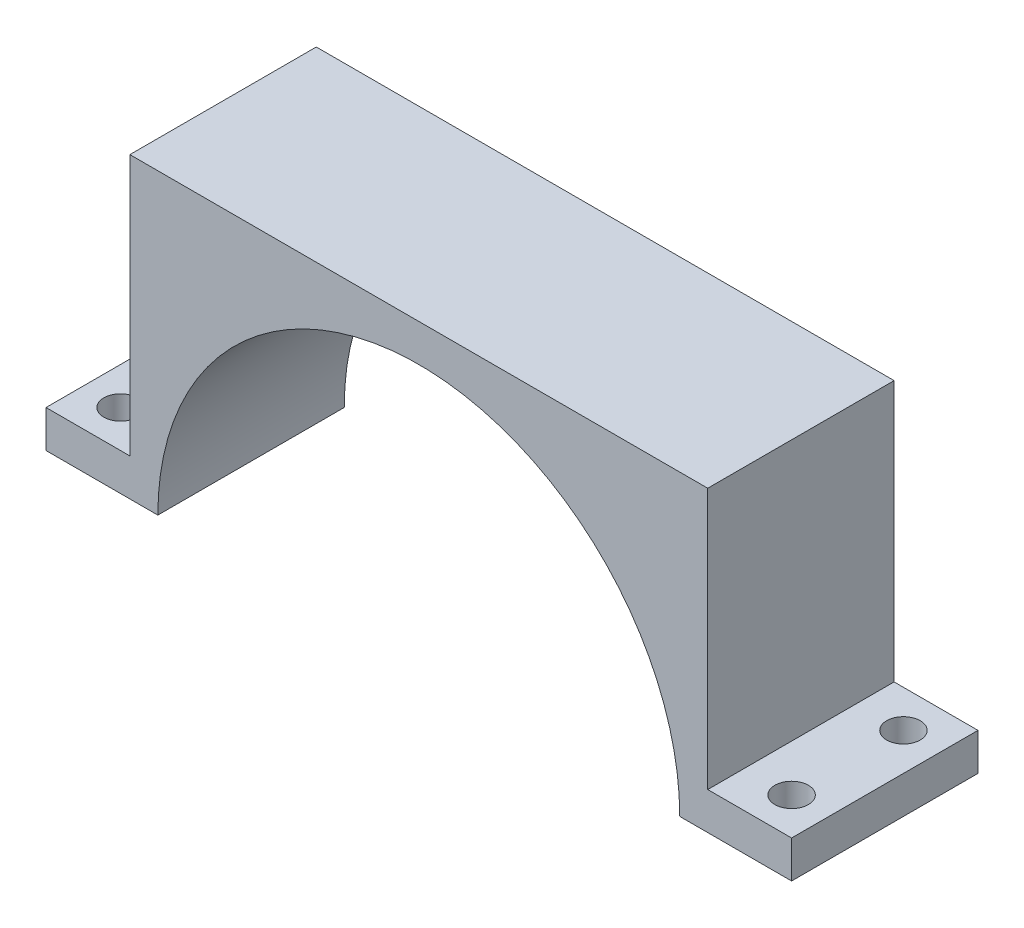
SolidWorks part; units mm, degrees
ref_plane "Płaszczyzna przednia" through (0, 0, 0) normal (0, 0, 1) x (1, 0, 0)
ref_plane "Płaszczyzna górna" through (0, 0, 0) normal (0, 1, 0) x (1, 0, 0)
ref_plane "Płaszczyzna prawa" through (0, 0, 0) normal (1, 0, 0) x (0, 0, -1)
sketch "Szkic1" plane through (0, 0, 0) normal (0, 0, 1) x (1, 0, 0)
  line L0 (70, 0) -> (100, 0)
  line L1 (100, 0) -> (100, 10)
  line L2 (100, 10) -> (77.5, 10)
  line L3 (77.5, 10) -> (77.5, 80)
  line L4 (77.5, 80) -> (-77.5, 80)
  line L5 (-77.5, 80) -> (-77.5, 10)
  line L6 (-77.5, 10) -> (-100, 10)
  line L7 (-100, 10) -> (-100, 0)
  line L8 (-100, 0) -> (-70, 0)
  line L9 (0, -15.2195) -> (0, 87.4692) construction
  arc A0 (-70, 0) -> (70, 0) centre (0, 0) cw
  point P16 (0, 80)
  dimension "D1" = 70
  dimension "D2" = 10
  dimension "D3" = 80
  dimension "D4" = 155
  dimension "D5" = 90
  dimension "D6" = 10
  dimension "D7" = 30
  dimension "D8" = 30
extrude "Dodanie-wyciągnięcie1" add sketch "Szkic1" along normal blind 50
ref_plane "Płaszczyzna1" through (0, 10, 0) normal (0, 1, 0) x (1, 0, 0)
sketch "Szkic2" plane through (0, 10, 0) normal (0, 1, 0) x (1, 0, 0)
  line L0 (-77.5, 0) -> (-100, 0) construction
  line L1 (-100, -50) -> (-100, 0) construction
  line L2 (-77.5, -50) -> (-100, -50) construction
  circle A0 centre (-90, -10) radius 4.5
  circle A1 centre (-90, -40) radius 4.5
  dimension "D1" = 10
  dimension "D3" = 10
  dimension "D4" = 10
  dimension "D2" = 10
extrude "Wytnij-wyciągnięcie1" cut sketch "Szkic2" against normal blind 50
mirror "Lustro1" about plane through (0, 0, 0) normal (1, 0, 0) of "Wytnij-wyciągnięcie1"
